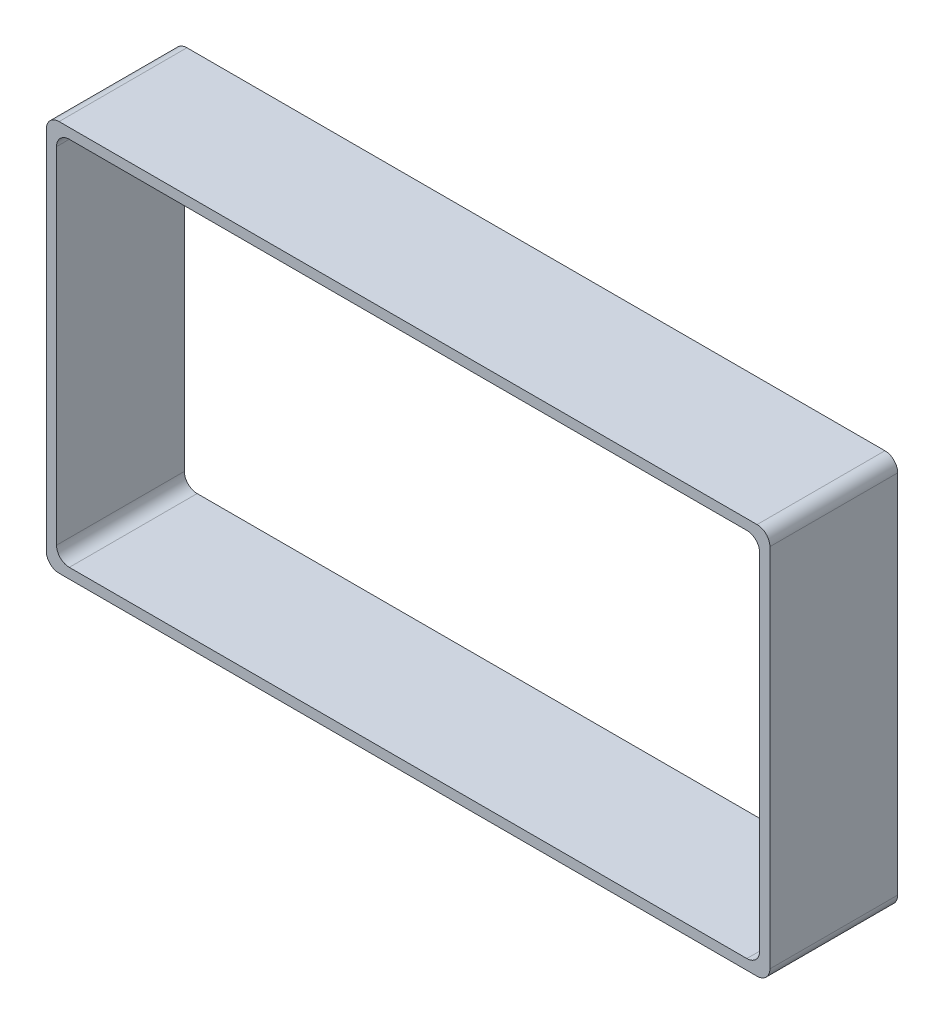
SolidWorks part; units mm, degrees
ref_plane "Plan de face" through (0, 0, 0) normal (0, 0, 1) x (1, 0, 0)
ref_plane "Plan de dessus" through (0, 0, 0) normal (0, 1, 0) x (1, 0, 0)
ref_plane "Plan de droite" through (0, 0, 0) normal (1, 0, 0) x (0, 0, -1)
sketch "Esquisse1" plane through (0, 0, 0) normal (0, 0, 1) x (1, 0, 0)
  line L0 (-28.3, 15.3) -> (28.3, 15.3)
  line L1 (-27.5, 14.5) -> (27.5, 14.5)
  line L2 (-27.5, 14.5) -> (-27.5, -14.5)
  line L3 (-27.5, -14.5) -> (27.5, -14.5)
  line L4 (27.5, 14.5) -> (27.5, -14.5)
  line L5 (-27.5, 14.5) -> (27.5, -14.5) construction
  line L6 (-27.5, -14.5) -> (27.5, 14.5) construction
  line L7 (28.3, 15.3) -> (28.3, -15.3)
  line L8 (-28.3, -15.3) -> (28.3, -15.3)
  line L9 (-28.3, 15.3) -> (-28.3, -15.3)
  point P0 (0, 0)
  dimension "D1" = 29
  dimension "D2" = 55
  dimension "D3" = 0.8
extrude "Boss.-Extru.1" add sketch "Esquisse1" along normal blind 10
fillet "Congé1" radius 1 8 edges at (-27.5, 14.5, 5) (-27.5, -14.5, 5) (27.5, -14.5, 5) (27.5, 14.5, 5) (28.3, -15.3, 5) (-28.3, -15.3, 5) (-28.3, 15.3, 5) (28.3, 15.3, 5)
